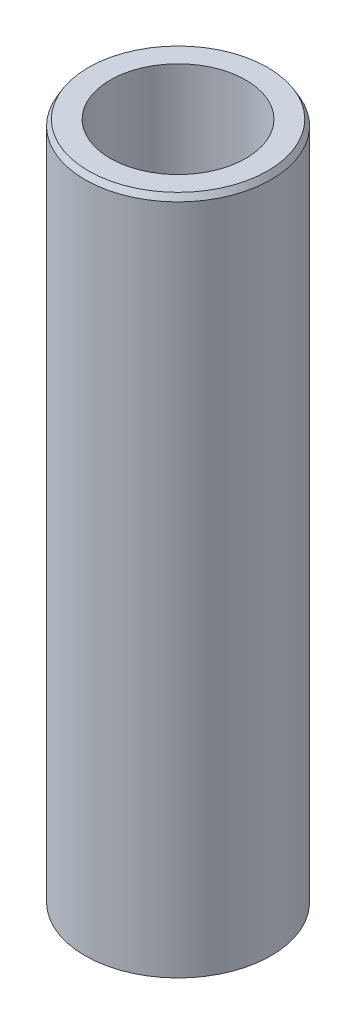
SolidWorks part; units mm, degrees
ref_plane "Front Plane" through (0, 0, 0) normal (0, 0, 1) x (1, 0, 0)
ref_plane "Top Plane" through (0, 0, 0) normal (0, 1, 0) x (1, 0, 0)
ref_plane "Right Plane" through (0, 0, 0) normal (1, 0, 0) x (0, 0, -1)
sketch "Sketch1" plane through (0, 0, 0) normal (0, 1, 0) x (1, 0, 0)
  circle A0 centre (0, 0) radius 12.5
  dimension "SHAFT_OD" = 25
extrude "Boss-Extrude1" add sketch "Sketch1" along normal blind 91.5576
sketch "Sketch2" plane through (0, 0, 0) normal (0, 1, 0) x (1, 0, 0)
  circle A0 centre (0, 0) radius 9.1198
  dimension "BORE_D" = 18.2396
extrude "Cut-Extrude1" cut sketch "Sketch2" along normal through all
chamfer "Chamfer1" distance 0.7909 angle 30 2 edges at (0, 91.5576, 12.5) (0, 0, 12.5) first distance on face at (0, 91.5576, 12.5) first distance on face at (0, 0, 9.1198)
